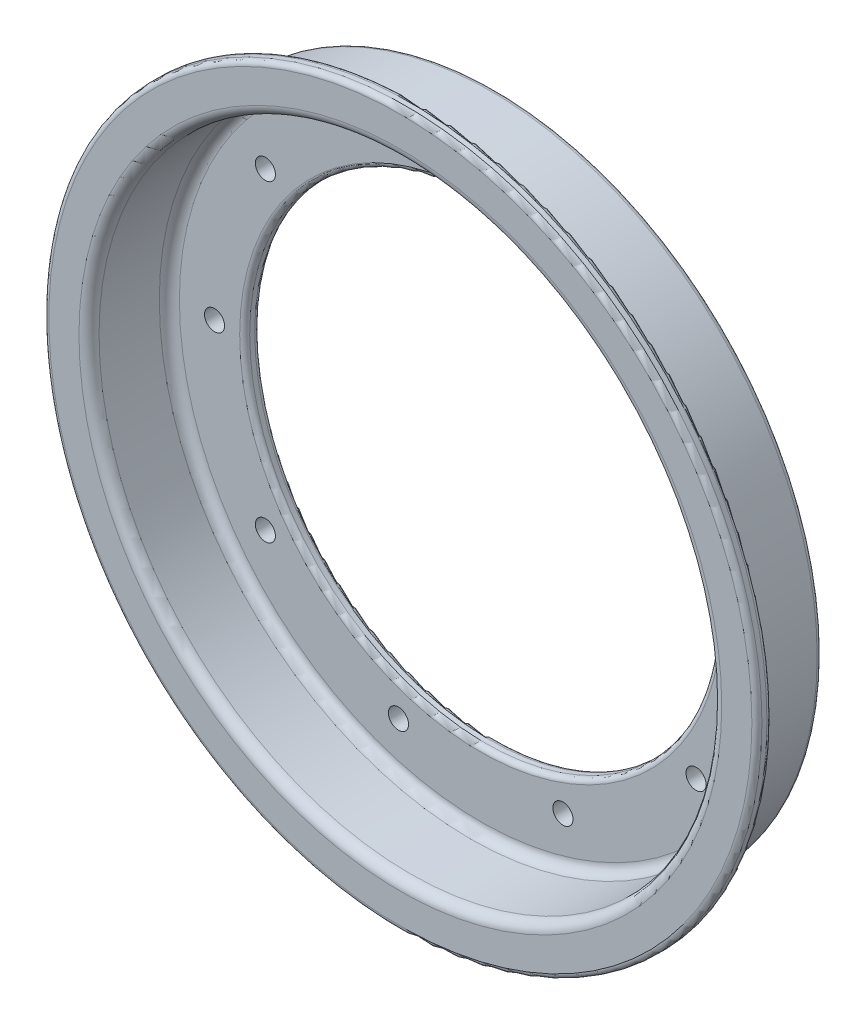
SolidWorks part; units mm, degrees
material "7075-T6 (SN)"
ref_plane "前视基准面" through (0, 0, 0) normal (0, 0, 1) x (1, 0, 0)
ref_plane "上视基准面" through (0, 0, 0) normal (0, 1, 0) x (1, 0, 0)
ref_plane "右视基准面" through (0, 0, 0) normal (1, 0, 0) x (0, 0, -1)
sketch "草图2" plane through (0, 0, 0) normal (0, 0, 1) x (1, 0, 0)
  circle A0 centre (0, 0) radius 65 construction
  circle A1 centre (0, 0) radius 65 construction
  circle A2 centre (0, 0) radius 71
  circle A4 centre (0, 0) radius 62
  dimension "D1" = 6
  dimension "D3" = 3
extrude "凸台-拉伸1" add sketch "草图2" along normal blind 3
sketch "草图3" plane through (0, 0, 0) normal (0, 0, -1) x (-1, 0, 0)
  circle A0 centre (0, 0) radius 65 construction
  circle A1 centre (0, 0) radius 62 construction
  circle A2 centre (0, 0) radius 65
  circle A3 centre (0, 0) radius 62
  circle M3 centre (0, 0) radius 62
extrude "凸台-拉伸2" add sketch "草图3" along normal offset from surface (16 mm away) 3 contours A2 M3 region at (63.1615, 0, 0) offset beyond the face yes
sketch "草图4" plane through (0, 0, -13) normal (0, 0, -1) x (-1, 0, 0)
  circle A0 centre (0, 0) radius 53 construction
  circle A1 centre (0, 0) radius 47
  circle A2 centre (0, 0) radius 65 construction
  circle A3 centre (0, 0) radius 65
  dimension "D1" = 6
extrude "凸台-拉伸3" add sketch "草图4" along normal blind 3
fillet "圆角1" radius 2 1 edges at (-62, 0, -13)
fillet "圆角2" radius 1 2 edges at (-47, 0, -13) (-47, 0, -16)
fillet "圆角3" radius 2 1 edges at (62, 0, 3)
fillet "圆角4" radius 1 2 edges at (71, 0, 0) (71, 0, 3)
fillet "圆角5" radius 1 1 edges at (-65, 0, -16)
sketch "草图5" plane through (0, 0, 3) normal (0, 0, 1) x (1, 0, 0)
  circle A0 centre (42.8779, 31.1526) radius 2
  circle A1 centre (53, 0) radius 2
  circle A2 centre (42.8779, -31.1526) radius 2
  circle A3 centre (16.3779, -50.406) radius 2
  circle A4 centre (-16.3779, -50.406) radius 2
  circle A5 centre (-42.8779, -31.1526) radius 2
  circle A6 centre (-53, 0) radius 2
  circle A7 centre (-42.8779, 31.1526) radius 2
  circle A8 centre (-16.3779, 50.406) radius 2
  circle A9 centre (16.3779, 50.406) radius 2
  point P24 (0, 0)
  dimension "D1" = 10
extrude "切除-拉伸1" cut sketch "草图5" against normal through all both and the other way through all
